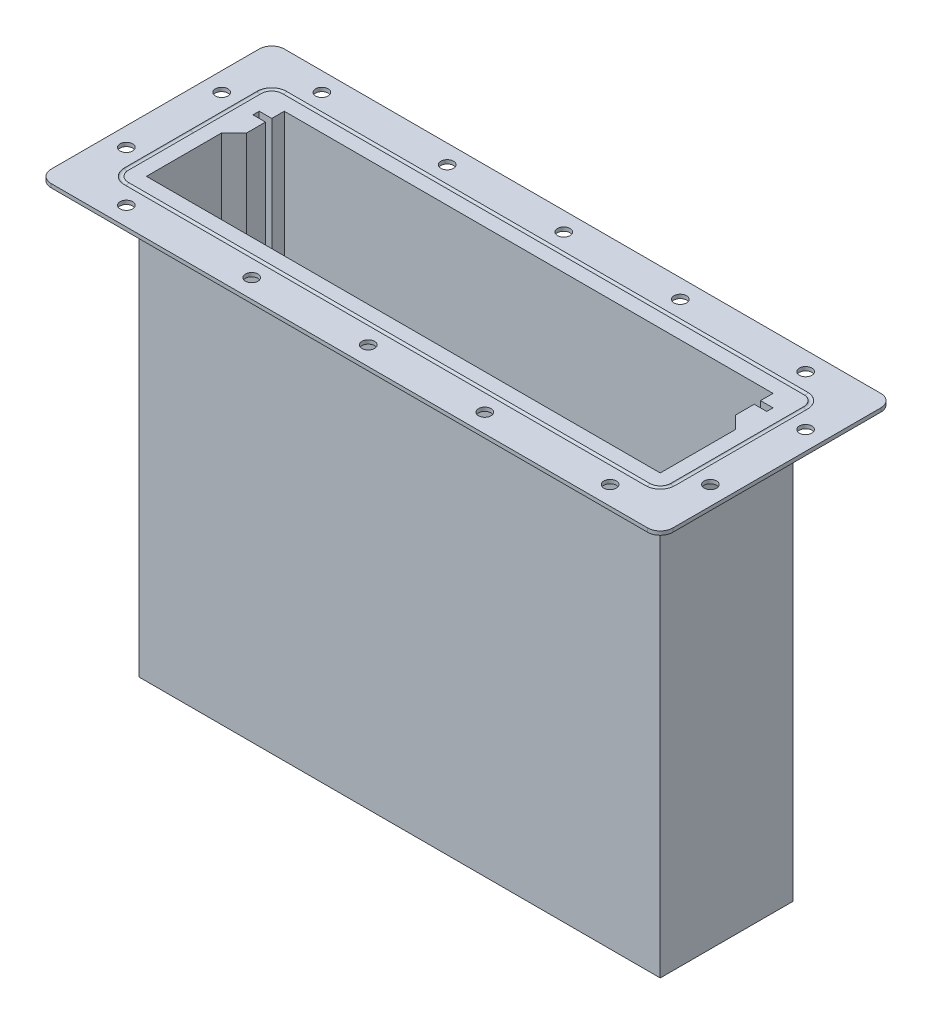
SolidWorks part; units mm, degrees
material "5052-H32"
ref_plane "Front Plane" through (0, 0, 0) normal (0, 0, 1) x (1, 0, 0)
ref_plane "Top Plane" through (0, 0, 0) normal (0, 1, 0) x (1, 0, 0)
ref_plane "Right Plane" through (0, 0, 0) normal (1, 0, 0) x (0, 0, -1)
sketch "Sketch1" plane through (0, 0, 0) normal (0, 1, 0) x (1, 0, 0)
  line L0 (-205, 40) -> (-195, 40)
  line L1 (-205, 50) -> (205, 50)
  line L2 (-205, 50) -> (-205, -50)
  line L3 (-205, -50) -> (205, -50)
  line L4 (205, 50) -> (205, -50)
  line L5 (-205, 50) -> (205, -50) construction
  line L6 (-205, -50) -> (205, 50) construction
  line L7 (-195, 40) -> (-195, 50)
  line L8 (0, 50) -> (0, -50) construction
  line L9 (-205, 35) -> (-195, 35)
  line L10 (-195, 35) -> (-195, 20)
  line L11 (-195, 20) -> (-205, 20)
  line L12 (-195, 20) -> (-205, 10)
  line L13 (195, 40) -> (195, 50)
  line L14 (205, 40) -> (195, 40)
  line L15 (205, 35) -> (195, 35)
  line L16 (195, 35) -> (195, 20)
  line L17 (195, 20) -> (205, 20)
  line L18 (195, 20) -> (205, 10)
  line L19 (-208, 53) -> (208, 53)
  line L20 (208, 53) -> (208, -53)
  line L21 (-208, -53) -> (208, -53)
  line L22 (-208, 53) -> (-208, -53)
  point P4 (0, 0)
  point P13 (-200, 20)
  point P24 (200, 20)
  dimension "D1" = 410
  dimension "D2" = 100
  dimension "D3" = 10
  dimension "D4" = 10
  dimension "D5" = 5
  dimension "D6" = 15
  dimension "D7" = 45
  dimension "D8" = 3
extrude "Boss-Extrude1" add sketch "Sketch1" along normal blind 3 contours L18 L16 L15 L4 L14 L13 L1 L7 L0 L2 L9 L10 L12 L3 region at (0, 0, 0.4682)
extrude "Boss-Extrude2" add sketch "Sketch1<3>" along normal blind 343 contours L12 L11 L2 | L19 L22 L21 L20 L1 L4 L3 L2 | L11 L10 L9 L2 | L0 L7 L1 L2 | L17 L18 L4 | L16 L17 L4 L15 | L14 L4 L1 L13 region at (-200, 0, -45) region at (-200, 0, -27.5) region at (-201.6667, 0, -16.6667) region at (200, 0, -45) region at (200, 0, -27.5) region at (201.6667, 0, -16.6667) region at (0, 0, -52.5707)
sketch "Sketch1<3>" plane through (0, 0, 0) normal (0, 1, 0) x (1, 0, 0) same geometry as "Sketch1"
sketch "Sketch2" plane through (0, 343, 0) normal (0, 1, 0) x (1, 0, 0)
  line L11 (-205, 40) -> (-195, 40)
  line L12 (-205, 40) -> (-195, 40) construction
  line L13 (-195, 40) -> (-195, 50)
  line L14 (-195, 50) -> (195, 50)
  line L15 (248, -93) -> (248, 93)
  line L16 (-248, -93) -> (248, -93)
  line L17 (-248, 93) -> (-248, -93)
  line L18 (248, 93) -> (-248, 93)
  line L19 (248, -83) -> (248, 83)
  line L20 (-238, -93) -> (238, -93)
  line L21 (-248, 83) -> (-248, -83)
  line L22 (238, 93) -> (-238, 93)
  line L23 (195, 50) -> (195, 40)
  line L24 (195, 40) -> (195, 50) construction
  line L25 (195, 40) -> (205, 40)
  line L26 (205, 40) -> (205, 35)
  line L27 (205, 35) -> (195, 35)
  line L28 (195, 35) -> (195, 20)
  line L29 (195, 20) -> (205, 10)
  line L30 (205, 10) -> (205, -50)
  line L31 (205, -50) -> (-205, -50)
  line L32 (-205, -50) -> (-205, 10)
  line L33 (-205, 10) -> (-195, 20)
  line L34 (-195, 20) -> (-195, 35)
  line L35 (-195, 35) -> (-205, 35)
  line L36 (-205, 35) -> (-205, 40)
  line L47 (-233, 78) -> (-233, -78) construction
  line L48 (-233, -78) -> (233, -78) construction
  line L49 (233, -78) -> (233, 78) construction
  line L50 (233, 78) -> (-233, 78) construction
  line L51 (218, -63) -> (218, 63)
  line L52 (-218, -63) -> (218, -63)
  line L53 (218, 63) -> (-218, 63)
  line L54 (-218, 63) -> (-218, -63)
  line L55 (218, -53) -> (218, 53)
  line L56 (-208, -63) -> (208, -63)
  line L57 (208, 63) -> (-208, 63)
  line L58 (-218, 53) -> (-218, -53)
  line L59 (-248, -93) -> (248, -93) construction
  line L60 (-248, 93) -> (-248, -93) construction
  line L61 (248, 93) -> (-248, 93) construction
  line L62 (248, -93) -> (248, 93) construction
  arc A0 (-238, -93) -> (-248, -83) centre (-238, -83) cw
  arc A1 (-248, 83) -> (-238, 93) centre (-238, 83) cw
  arc A2 (248, -83) -> (238, -93) centre (238, -83) cw
  arc A3 (248, 83) -> (238, 93) centre (238, 83) ccw
  circle A4 centre (-233, 38) radius 5
  circle A5 centre (-233, -38) radius 5
  circle A6 centre (-193, -78) radius 5
  circle A7 centre (-193, 78) radius 5
  circle A8 centre (193, 78) radius 5
  circle A9 centre (233, 38) radius 5
  circle A10 centre (233, -38) radius 5
  circle A11 centre (193, -78) radius 5
  circle A12 centre (93, -78) radius 5
  circle A13 centre (-93, -78) radius 5
  circle A14 centre (-93, 78) radius 5
  circle A15 centre (93, 78) radius 5
  circle A16 centre (0, 78) radius 5
  circle A17 centre (0, -78) radius 5
  arc A18 (218, -53) -> (208, -63) centre (208, -53) cw
  arc A19 (218, 53) -> (208, 63) centre (208, 53) ccw
  arc A20 (-218, -53) -> (-208, -63) centre (-208, -53) ccw
  arc A21 (-218, 53) -> (-208, 63) centre (-208, 53) cw
  line M5 (-195, 40) -> (-195, 50)
  line M6 (-195, 50) -> (195, 50)
  line M7 (195, 50) -> (195, 40)
  line M8 (195, 40) -> (205, 40)
  line M9 (205, 40) -> (205, 35)
  line M10 (205, 35) -> (195, 35)
  line M11 (195, 35) -> (195, 20)
  line M12 (195, 20) -> (205, 10)
  line M13 (205, 10) -> (205, -50)
  line M14 (205, -50) -> (-205, -50)
  line M15 (-205, -50) -> (-205, 10)
  line M16 (-205, 10) -> (-195, 20)
  line M17 (-195, 20) -> (-195, 35)
  line M18 (-195, 35) -> (-205, 35)
  line M19 (-205, 35) -> (-205, 40)
  line M20 (-205, 40) -> (-195, 40)
  line M21 (208, 53) -> (-208, 53)
  line M22 (-208, 53) -> (-208, -53)
  line M23 (-208, -53) -> (208, -53)
  line M24 (208, -53) -> (208, 53)
  dimension "D4" = 10
  dimension "D5" = 10
  dimension "D13" = 10
  dimension "D6" = 40
  dimension "D7" = 40
  dimension "D8" = 40
  dimension "D9" = 40
  dimension "D10" = 100
  dimension "D11" = 100
  dimension "D12" = 93
  dimension "D1" = 40
  dimension "D2" = 10
  dimension "D3" = 15
extrude "Boss-Extrude3" add sketch "Sketch2" along normal blind 3 contours L19 A3 L22 A1 L21 A0 L20 A2 A4 A5 A6 A7 A8 A9 A10 A11 A12 A13 A14 A15 A16 A17 L58 A21 L57 A19 L55 A18 L56 A20 | A21 L58 A20 L56 A18 L55 A19 L57 M21 M24 M23 M22 | M24 M21 M22 M23 M20 M5 M6 M7 M8 M9 M10 M11 M12 M13 M14 M15 M16 M17 M18 M19 region at (241.3253, 343, 86.3253) region at (215.7663, 343, 60.7663) region at (211.8619, 343, 56.8619) region at (215.7663, 343, -60.7663) region at (-215.7663, 343, 60.7663) region at (-215.7663, 343, -60.7663) region at (207.5707, 343, 0)
sketch "Sketch3" plane through (0, 0, 0) normal (0, 0, 1) x (1, 0, 0)
  line L0 (-218, 343) -> (-218, 346)
  line L1 (-233, 343) -> (233, 343) construction
  line L3 (-216.4, 346) -> (-219.6, 346)
  ellipse E0 centre (-218, 346) end of major axis (-216.4, 346) minor radius 1
  dimension "D1" = 2
  dimension "D2" = 3.2
  dimension "D3" = 3
sketch "Sketch4" plane through (0, 346, 0) normal (0, 1, 0) x (1, 0, 0)
  line L0 (-208, 63) -> (208, 63)
  line L1 (218, 53) -> (218, -53)
  line L2 (208, -63) -> (-208, -63)
  line L3 (-218, -53) -> (-218, 53)
  arc A0 (-208, -63) -> (-218, -53) centre (-208, -53) cw
  arc A1 (218, -53) -> (208, -63) centre (208, -53) cw
  arc A2 (208, 63) -> (218, 53) centre (208, 53) cw
  arc A3 (-208, 63) -> (-218, 53) centre (-208, 53) ccw
  dimension "D1" = 10
sweep "Cut-Sweep2" cut profiles "Sketch3" path "Sketch4"
